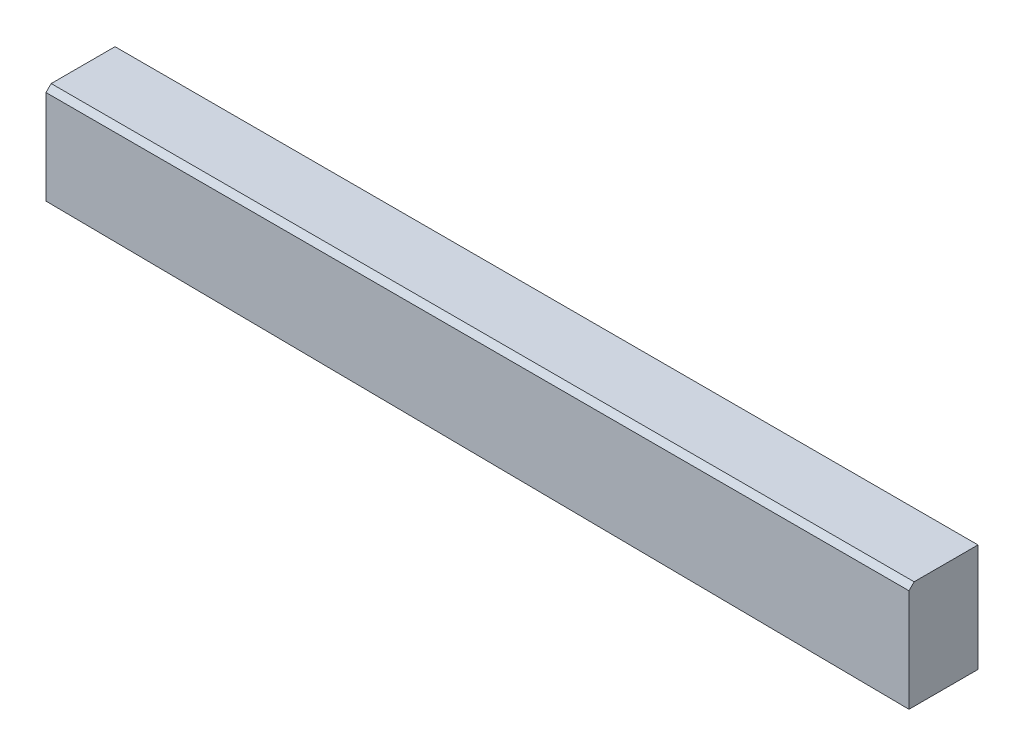
SolidWorks part; units mm, degrees
ref_plane "Front" through (0, 0, 0) normal (0, 0, 1) x (1, 0, 0)
ref_plane "Top" through (0, 0, 0) normal (0, 1, 0) x (1, 0, 0)
ref_plane "Right" through (0, 0, 0) normal (1, 0, 0) x (0, 0, -1)
sketch "Sketch1" plane through (0, 0, 0) normal (0, 0, 1) x (1, 0, 0)
  line L0 (-132.2194, 0) -> (126.609, 0) construction
  line L1 (-100, 24) -> (0, 24)
  line L2 (0, 24) -> (0, 11.5)
  line L3 (0, 11.5) -> (-100, 12.5)
  line L4 (-100, 12.5) -> (-100, 24)
  line L5 (0, 11.5) -> (0, 0)
  line L6 (0, 104.5412) -> (0, -23.7509) construction
  dimension "D3" = 0.573
extrude "BaseKey" add sketch "Sketch1" along normal mid plane 8 contours L3 L4 L1 L2
chamfer "Chamfer1" distance 0.6 angle 45 1 edges at (-50, 24, 4)
equation "\"D3@Sketch1\" = 1.8 /  pi "
